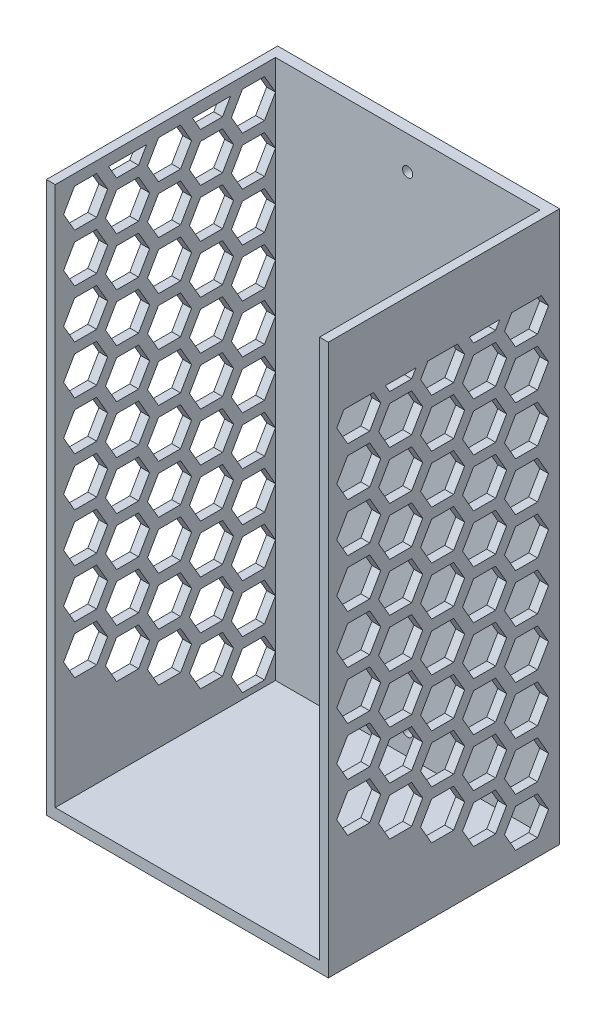
SolidWorks part; units mm, degrees
ref_plane "Front Plane" through (0, 0, 0) normal (0, 0, 1) x (1, 0, 0)
ref_plane "Top Plane" through (0, 0, 0) normal (0, 1, 0) x (1, 0, 0)
ref_plane "Right Plane" through (0, 0, 0) normal (1, 0, 0) x (0, 0, -1)
sketch "Sketch1" plane through (0, 0, 0) normal (0, 0, 1) x (1, 0, 0)
  line L1 (-64, -125) -> (64, -125)
  line L2 (-64, -125) -> (-64, 125)
  line L3 (-64, 125) -> (64, 125)
  line L4 (64, -125) -> (64, 125)
  line L5 (-64, -125) -> (64, 125) construction
  line L6 (-64, 125) -> (64, -125) construction
  point P0 (0, 0)
  dimension "D1" = 128
  dimension "D2" = 250
extrude "Boss-Extrude1" add sketch "Sketch1" along normal blind 5
sketch "Sketch2" plane through (0, 0, 0) normal (0, 0, 1) x (1, 0, 0)
  line L0 (64, 125) -> (-64, 125) construction
  line L1 (-64, -125) -> (64, -125) construction
  circle A0 centre (0, 110) radius 2.3
  circle A1 centre (0, -110) radius 2.3
  dimension "D1" = 4.6
  dimension "D2" = 15
  dimension "D3" = 15
extrude "Cut-Extrude2" cut sketch "Sketch2" along normal through all
sketch "Sketch3" plane through (0, 0, 5) normal (0, 0, 1) x (1, 0, 0)
  line L0 (-64, 125) -> (-64, -125) construction
  line L1 (-64, -121) -> (64, -121)
  line L2 (-64, -121) -> (-64, -125)
  line L3 (-64, -125) -> (64, -125)
  line L4 (64, -121) -> (64, -125)
  dimension "D1" = 4
extrude "Boss-Extrude2" add sketch "Sketch3" along normal blind 100
sketch "Sketch4" plane through (0, 0, 5) normal (0, 0, 1) x (1, 0, 0)
  line L0 (64, -121) -> (-64, -121) construction
  line L1 (-64, 125) -> (-60, 125)
  line L2 (-64, 125) -> (-64, -121)
  line L3 (-64, -121) -> (-60, -121)
  line L4 (-60, 125) -> (-60, -121)
  line L5 (64, -121) -> (-64, -121) construction
  line L6 (64, 125) -> (60, 125)
  line L7 (64, 125) -> (64, -121)
  line L8 (64, -121) -> (60, -121)
  line L9 (60, 125) -> (60, -121)
  dimension "D1" = 4
  dimension "D2" = 4
extrude "Boss-Extrude3" add sketch "Sketch4" along normal up to surface (100 mm away) up to face at (0, -123, 105)
sketch "Sketch5" plane through (-64, 0, 0) normal (-1, 0, 0) x (0, 0, 1)
  line L0 (20, -100) -> (10, -100)
  line L1 (20, 120) -> (10, 120)
  line L2 (10, 120) -> (5, 111.3397)
  line L3 (5, 111.3397) -> (10, 102.6795)
  line L4 (10, 102.6795) -> (20, 102.6795)
  line L5 (20, 102.6795) -> (25, 111.3397)
  line L6 (25, 111.3397) -> (20, 120)
  line L7 (0, 125) -> (0, -125) construction
  line L8 (39.0526, 131) -> (29.0526, 131)
  line L9 (29.0526, 131) -> (24.0526, 122.3397)
  line L10 (24.0526, 122.3397) -> (29.0526, 113.6795)
  line L11 (29.0526, 113.6795) -> (39.0526, 113.6795)
  line L12 (39.0526, 113.6795) -> (44.0526, 122.3397)
  line L13 (44.0526, 122.3397) -> (39.0526, 131)
  line L14 (58.1051, 142) -> (48.1051, 142)
  line L15 (48.1051, 142) -> (43.1051, 133.3397)
  line L16 (43.1051, 133.3397) -> (48.1051, 124.6795)
  line L17 (48.1051, 124.6795) -> (58.1051, 124.6795)
  line L18 (58.1051, 124.6795) -> (63.1051, 133.3397)
  line L19 (63.1051, 133.3397) -> (58.1051, 142)
  line L20 (77.1577, 153) -> (67.1577, 153)
  line L21 (67.1577, 153) -> (62.1577, 144.3397)
  line L22 (62.1577, 144.3397) -> (67.1577, 135.6795)
  line L23 (67.1577, 135.6795) -> (77.1577, 135.6795)
  line L24 (77.1577, 135.6795) -> (82.1577, 144.3397)
  line L25 (82.1577, 144.3397) -> (77.1577, 153)
  line L26 (96.2102, 164) -> (86.2102, 164)
  line L27 (86.2102, 164) -> (81.2102, 155.3397)
  line L28 (81.2102, 155.3397) -> (86.2102, 146.6795)
  line L29 (86.2102, 146.6795) -> (96.2102, 146.6795)
  line L30 (96.2102, 146.6795) -> (101.2102, 155.3397)
  line L31 (101.2102, 155.3397) -> (96.2102, 164)
  line L44 (39.0526, 109) -> (29.0526, 109)
  line L45 (29.0526, 109) -> (24.0526, 100.3397)
  line L46 (24.0526, 100.3397) -> (29.0526, 91.6795)
  line L47 (29.0526, 91.6795) -> (39.0526, 91.6795)
  line L48 (39.0526, 91.6795) -> (44.0526, 100.3397)
  line L49 (44.0526, 100.3397) -> (39.0526, 109)
  line L50 (58.1051, 120) -> (48.1051, 120)
  line L51 (48.1051, 120) -> (43.1051, 111.3397)
  line L52 (43.1051, 111.3397) -> (48.1051, 102.6795)
  line L53 (48.1051, 102.6795) -> (58.1051, 102.6795)
  line L54 (58.1051, 102.6795) -> (63.1051, 111.3397)
  line L55 (63.1051, 111.3397) -> (58.1051, 120)
  line L56 (77.1577, 131) -> (67.1577, 131)
  line L57 (67.1577, 131) -> (62.1577, 122.3397)
  line L58 (62.1577, 122.3397) -> (67.1577, 113.6795)
  line L59 (67.1577, 113.6795) -> (77.1577, 113.6795)
  line L60 (77.1577, 113.6795) -> (82.1577, 122.3397)
  line L61 (82.1577, 122.3397) -> (77.1577, 131)
  line L62 (96.2102, 142) -> (86.2102, 142)
  line L63 (86.2102, 142) -> (81.2102, 133.3397)
  line L64 (81.2102, 133.3397) -> (86.2102, 124.6795)
  line L65 (86.2102, 124.6795) -> (96.2102, 124.6795)
  line L66 (96.2102, 124.6795) -> (101.2102, 133.3397)
  line L67 (101.2102, 133.3397) -> (96.2102, 142)
  line L80 (39.0526, 87) -> (29.0526, 87)
  line L81 (29.0526, 87) -> (24.0526, 78.3397)
  line L82 (24.0526, 78.3397) -> (29.0526, 69.6795)
  line L83 (29.0526, 69.6795) -> (39.0526, 69.6795)
  line L84 (39.0526, 69.6795) -> (44.0526, 78.3397)
  line L85 (44.0526, 78.3397) -> (39.0526, 87)
  line L86 (58.1051, 98) -> (48.1051, 98)
  line L87 (48.1051, 98) -> (43.1051, 89.3397)
  line L88 (43.1051, 89.3397) -> (48.1051, 80.6795)
  line L89 (48.1051, 80.6795) -> (58.1051, 80.6795)
  line L90 (58.1051, 80.6795) -> (63.1051, 89.3397)
  line L91 (63.1051, 89.3397) -> (58.1051, 98)
  line L92 (77.1577, 109) -> (67.1577, 109)
  line L93 (67.1577, 109) -> (62.1577, 100.3397)
  line L94 (62.1577, 100.3397) -> (67.1577, 91.6795)
  line L95 (67.1577, 91.6795) -> (77.1577, 91.6795)
  line L96 (77.1577, 91.6795) -> (82.1577, 100.3397)
  line L97 (82.1577, 100.3397) -> (77.1577, 109)
  line L98 (96.2102, 120) -> (86.2102, 120)
  line L99 (86.2102, 120) -> (81.2102, 111.3397)
  line L100 (81.2102, 111.3397) -> (86.2102, 102.6795)
  line L101 (86.2102, 102.6795) -> (96.2102, 102.6795)
  line L102 (96.2102, 102.6795) -> (101.2102, 111.3397)
  line L103 (101.2102, 111.3397) -> (96.2102, 120)
  line L116 (39.0526, 65) -> (29.0526, 65)
  line L117 (29.0526, 65) -> (24.0526, 56.3397)
  line L118 (24.0526, 56.3397) -> (29.0526, 47.6795)
  line L119 (29.0526, 47.6795) -> (39.0526, 47.6795)
  line L120 (39.0526, 47.6795) -> (44.0526, 56.3397)
  line L121 (44.0526, 56.3397) -> (39.0526, 65)
  line L122 (58.1051, 76) -> (48.1051, 76)
  line L123 (48.1051, 76) -> (43.1051, 67.3397)
  line L124 (43.1051, 67.3397) -> (48.1051, 58.6795)
  line L125 (48.1051, 58.6795) -> (58.1051, 58.6795)
  line L126 (58.1051, 58.6795) -> (63.1051, 67.3397)
  line L127 (63.1051, 67.3397) -> (58.1051, 76)
  line L128 (77.1577, 87) -> (67.1577, 87)
  line L129 (67.1577, 87) -> (62.1577, 78.3397)
  line L130 (62.1577, 78.3397) -> (67.1577, 69.6795)
  line L131 (67.1577, 69.6795) -> (77.1577, 69.6795)
  line L132 (77.1577, 69.6795) -> (82.1577, 78.3397)
  line L133 (82.1577, 78.3397) -> (77.1577, 87)
  line L134 (96.2102, 98) -> (86.2102, 98)
  line L135 (86.2102, 98) -> (81.2102, 89.3397)
  line L136 (81.2102, 89.3397) -> (86.2102, 80.6795)
  line L137 (86.2102, 80.6795) -> (96.2102, 80.6795)
  line L138 (96.2102, 80.6795) -> (101.2102, 89.3397)
  line L139 (101.2102, 89.3397) -> (96.2102, 98)
  line L152 (39.0526, 43) -> (29.0526, 43)
  line L153 (29.0526, 43) -> (24.0526, 34.3397)
  line L154 (24.0526, 34.3397) -> (29.0526, 25.6795)
  line L155 (29.0526, 25.6795) -> (39.0526, 25.6795)
  line L156 (39.0526, 25.6795) -> (44.0526, 34.3397)
  line L157 (44.0526, 34.3397) -> (39.0526, 43)
  line L158 (58.1051, 54) -> (48.1051, 54)
  line L159 (48.1051, 54) -> (43.1051, 45.3397)
  line L160 (43.1051, 45.3397) -> (48.1051, 36.6795)
  line L161 (48.1051, 36.6795) -> (58.1051, 36.6795)
  line L162 (58.1051, 36.6795) -> (63.1051, 45.3397)
  line L163 (63.1051, 45.3397) -> (58.1051, 54)
  line L164 (77.1577, 65) -> (67.1577, 65)
  line L165 (67.1577, 65) -> (62.1577, 56.3397)
  line L166 (62.1577, 56.3397) -> (67.1577, 47.6795)
  line L167 (67.1577, 47.6795) -> (77.1577, 47.6795)
  line L168 (77.1577, 47.6795) -> (82.1577, 56.3397)
  line L169 (82.1577, 56.3397) -> (77.1577, 65)
  line L170 (96.2102, 76) -> (86.2102, 76)
  line L171 (86.2102, 76) -> (81.2102, 67.3397)
  line L172 (81.2102, 67.3397) -> (86.2102, 58.6795)
  line L173 (86.2102, 58.6795) -> (96.2102, 58.6795)
  line L174 (96.2102, 58.6795) -> (101.2102, 67.3397)
  line L175 (101.2102, 67.3397) -> (96.2102, 76)
  line L188 (39.0526, 21) -> (29.0526, 21)
  line L189 (29.0526, 21) -> (24.0526, 12.3397)
  line L190 (24.0526, 12.3397) -> (29.0526, 3.6795)
  line L191 (29.0526, 3.6795) -> (39.0526, 3.6795)
  line L192 (39.0526, 3.6795) -> (44.0526, 12.3397)
  line L193 (44.0526, 12.3397) -> (39.0526, 21)
  line L194 (58.1051, 32) -> (48.1051, 32)
  line L195 (48.1051, 32) -> (43.1051, 23.3397)
  line L196 (43.1051, 23.3397) -> (48.1051, 14.6795)
  line L197 (48.1051, 14.6795) -> (58.1051, 14.6795)
  line L198 (58.1051, 14.6795) -> (63.1051, 23.3397)
  line L199 (63.1051, 23.3397) -> (58.1051, 32)
  line L200 (77.1577, 43) -> (67.1577, 43)
  line L201 (67.1577, 43) -> (62.1577, 34.3397)
  line L202 (62.1577, 34.3397) -> (67.1577, 25.6795)
  line L203 (67.1577, 25.6795) -> (77.1577, 25.6795)
  line L204 (77.1577, 25.6795) -> (82.1577, 34.3397)
  line L205 (82.1577, 34.3397) -> (77.1577, 43)
  line L206 (96.2102, 54) -> (86.2102, 54)
  line L207 (86.2102, 54) -> (81.2102, 45.3397)
  line L208 (81.2102, 45.3397) -> (86.2102, 36.6795)
  line L209 (86.2102, 36.6795) -> (96.2102, 36.6795)
  line L210 (96.2102, 36.6795) -> (101.2102, 45.3397)
  line L211 (101.2102, 45.3397) -> (96.2102, 54)
  line L224 (39.0526, -1) -> (29.0526, -1)
  line L225 (29.0526, -1) -> (24.0526, -9.6603)
  line L226 (24.0526, -9.6603) -> (29.0526, -18.3205)
  line L227 (29.0526, -18.3205) -> (39.0526, -18.3205)
  line L228 (39.0526, -18.3205) -> (44.0526, -9.6603)
  line L229 (44.0526, -9.6603) -> (39.0526, -1)
  line L230 (58.1051, 10) -> (48.1051, 10)
  line L231 (48.1051, 10) -> (43.1051, 1.3397)
  line L232 (43.1051, 1.3397) -> (48.1051, -7.3205)
  line L233 (48.1051, -7.3205) -> (58.1051, -7.3205)
  line L234 (58.1051, -7.3205) -> (63.1051, 1.3397)
  line L235 (63.1051, 1.3397) -> (58.1051, 10)
  line L236 (77.1577, 21) -> (67.1577, 21)
  line L237 (67.1577, 21) -> (62.1577, 12.3397)
  line L238 (62.1577, 12.3397) -> (67.1577, 3.6795)
  line L239 (67.1577, 3.6795) -> (77.1577, 3.6795)
  line L240 (77.1577, 3.6795) -> (82.1577, 12.3397)
  line L241 (82.1577, 12.3397) -> (77.1577, 21)
  line L242 (96.2102, 32) -> (86.2102, 32)
  line L243 (86.2102, 32) -> (81.2102, 23.3397)
  line L244 (81.2102, 23.3397) -> (86.2102, 14.6795)
  line L245 (86.2102, 14.6795) -> (96.2102, 14.6795)
  line L246 (96.2102, 14.6795) -> (101.2102, 23.3397)
  line L247 (101.2102, 23.3397) -> (96.2102, 32)
  line L260 (39.0526, -23) -> (29.0526, -23)
  line L261 (29.0526, -23) -> (24.0526, -31.6603)
  line L262 (24.0526, -31.6603) -> (29.0526, -40.3205)
  line L263 (29.0526, -40.3205) -> (39.0526, -40.3205)
  line L264 (39.0526, -40.3205) -> (44.0526, -31.6603)
  line L265 (44.0526, -31.6603) -> (39.0526, -23)
  line L266 (58.1051, -12) -> (48.1051, -12)
  line L267 (48.1051, -12) -> (43.1051, -20.6603)
  line L268 (43.1051, -20.6603) -> (48.1051, -29.3205)
  line L269 (48.1051, -29.3205) -> (58.1051, -29.3205)
  line L270 (58.1051, -29.3205) -> (63.1051, -20.6603)
  line L271 (63.1051, -20.6603) -> (58.1051, -12)
  line L272 (77.1577, -1) -> (67.1577, -1)
  line L273 (67.1577, -1) -> (62.1577, -9.6603)
  line L274 (62.1577, -9.6603) -> (67.1577, -18.3205)
  line L275 (67.1577, -18.3205) -> (77.1577, -18.3205)
  line L276 (77.1577, -18.3205) -> (82.1577, -9.6603)
  line L277 (82.1577, -9.6603) -> (77.1577, -1)
  line L278 (96.2102, 10) -> (86.2102, 10)
  line L279 (86.2102, 10) -> (81.2102, 1.3397)
  line L280 (81.2102, 1.3397) -> (86.2102, -7.3205)
  line L281 (86.2102, -7.3205) -> (96.2102, -7.3205)
  line L282 (96.2102, -7.3205) -> (101.2102, 1.3397)
  line L283 (101.2102, 1.3397) -> (96.2102, 10)
  line L296 (39.0526, -45) -> (29.0526, -45)
  line L297 (29.0526, -45) -> (24.0526, -53.6603)
  line L298 (24.0526, -53.6603) -> (29.0526, -62.3205)
  line L299 (29.0526, -62.3205) -> (39.0526, -62.3205)
  line L300 (39.0526, -62.3205) -> (44.0526, -53.6603)
  line L301 (44.0526, -53.6603) -> (39.0526, -45)
  line L302 (58.1051, -34) -> (48.1051, -34)
  line L303 (48.1051, -34) -> (43.1051, -42.6603)
  line L304 (43.1051, -42.6603) -> (48.1051, -51.3205)
  line L305 (48.1051, -51.3205) -> (58.1051, -51.3205)
  line L306 (58.1051, -51.3205) -> (63.1051, -42.6603)
  line L307 (63.1051, -42.6603) -> (58.1051, -34)
  line L308 (77.1577, -23) -> (67.1577, -23)
  line L309 (67.1577, -23) -> (62.1577, -31.6603)
  line L310 (62.1577, -31.6603) -> (67.1577, -40.3205)
  line L311 (67.1577, -40.3205) -> (77.1577, -40.3205)
  line L312 (77.1577, -40.3205) -> (82.1577, -31.6603)
  line L313 (82.1577, -31.6603) -> (77.1577, -23)
  line L314 (96.2102, -12) -> (86.2102, -12)
  line L315 (86.2102, -12) -> (81.2102, -20.6603)
  line L316 (81.2102, -20.6603) -> (86.2102, -29.3205)
  line L317 (86.2102, -29.3205) -> (96.2102, -29.3205)
  line L318 (96.2102, -29.3205) -> (101.2102, -20.6603)
  line L319 (101.2102, -20.6603) -> (96.2102, -12)
  line L332 (39.0526, -67) -> (29.0526, -67)
  line L333 (29.0526, -67) -> (24.0526, -75.6603)
  line L334 (24.0526, -75.6603) -> (29.0526, -84.3205)
  line L335 (29.0526, -84.3205) -> (39.0526, -84.3205)
  line L336 (39.0526, -84.3205) -> (44.0526, -75.6603)
  line L337 (44.0526, -75.6603) -> (39.0526, -67)
  line L338 (58.1051, -56) -> (48.1051, -56)
  line L339 (48.1051, -56) -> (43.1051, -64.6603)
  line L340 (43.1051, -64.6603) -> (48.1051, -73.3205)
  line L341 (48.1051, -73.3205) -> (58.1051, -73.3205)
  line L342 (58.1051, -73.3205) -> (63.1051, -64.6603)
  line L343 (63.1051, -64.6603) -> (58.1051, -56)
  line L344 (77.1577, -45) -> (67.1577, -45)
  line L345 (67.1577, -45) -> (62.1577, -53.6603)
  line L346 (62.1577, -53.6603) -> (67.1577, -62.3205)
  line L347 (67.1577, -62.3205) -> (77.1577, -62.3205)
  line L348 (77.1577, -62.3205) -> (82.1577, -53.6603)
  line L349 (82.1577, -53.6603) -> (77.1577, -45)
  line L350 (96.2102, -34) -> (86.2102, -34)
  line L351 (86.2102, -34) -> (81.2102, -42.6603)
  line L352 (81.2102, -42.6603) -> (86.2102, -51.3205)
  line L353 (86.2102, -51.3205) -> (96.2102, -51.3205)
  line L354 (96.2102, -51.3205) -> (101.2102, -42.6603)
  line L355 (101.2102, -42.6603) -> (96.2102, -34)
  line L512 (20, 98) -> (10, 98)
  line L513 (10, 98) -> (5, 89.3397)
  line L514 (5, 89.3397) -> (10, 80.6795)
  line L515 (10, 80.6795) -> (20, 80.6795)
  line L516 (20, 80.6795) -> (25, 89.3397)
  line L517 (25, 89.3397) -> (20, 98)
  line L518 (20, 76) -> (10, 76)
  line L519 (10, 76) -> (5, 67.3397)
  line L520 (5, 67.3397) -> (10, 58.6795)
  line L521 (10, 58.6795) -> (20, 58.6795)
  line L522 (20, 58.6795) -> (25, 67.3397)
  line L523 (25, 67.3397) -> (20, 76)
  line L524 (20, 54) -> (10, 54)
  line L525 (10, 54) -> (5, 45.3397)
  line L526 (5, 45.3397) -> (10, 36.6795)
  line L527 (10, 36.6795) -> (20, 36.6795)
  line L528 (20, 36.6795) -> (25, 45.3397)
  line L529 (25, 45.3397) -> (20, 54)
  line L530 (20, 32) -> (10, 32)
  line L531 (10, 32) -> (5, 23.3397)
  line L532 (5, 23.3397) -> (10, 14.6795)
  line L533 (10, 14.6795) -> (20, 14.6795)
  line L534 (20, 14.6795) -> (25, 23.3397)
  line L535 (25, 23.3397) -> (20, 32)
  line L536 (20, 10) -> (10, 10)
  line L537 (10, 10) -> (5, 1.3397)
  line L538 (5, 1.3397) -> (10, -7.3205)
  line L539 (10, -7.3205) -> (20, -7.3205)
  line L540 (20, -7.3205) -> (25, 1.3397)
  line L541 (25, 1.3397) -> (20, 10)
  line L542 (20, -12) -> (10, -12)
  line L543 (10, -12) -> (5, -20.6603)
  line L544 (5, -20.6603) -> (10, -29.3205)
  line L545 (10, -29.3205) -> (20, -29.3205)
  line L546 (20, -29.3205) -> (25, -20.6603)
  line L547 (25, -20.6603) -> (20, -12)
  line L548 (20, -34) -> (10, -34)
  line L549 (10, -34) -> (5, -42.6603)
  line L550 (5, -42.6603) -> (10, -51.3205)
  line L551 (10, -51.3205) -> (20, -51.3205)
  line L552 (20, -51.3205) -> (25, -42.6603)
  line L553 (25, -42.6603) -> (20, -34)
  line L554 (20, -56) -> (10, -56)
  line L555 (10, -56) -> (5, -64.6603)
  line L556 (5, -64.6603) -> (10, -73.3205)
  line L557 (10, -73.3205) -> (20, -73.3205)
  line L558 (20, -73.3205) -> (25, -64.6603)
  line L559 (25, -64.6603) -> (20, -56)
  line L560 (20, -78) -> (10, -78)
  line L561 (10, -78) -> (5, -86.6603)
  line L562 (5, -86.6603) -> (10, -95.3205)
  line L563 (10, -95.3205) -> (20, -95.3205)
  line L564 (20, -95.3205) -> (25, -86.6603)
  line L565 (25, -86.6603) -> (20, -78)
  line L590 (20, 120) -> (39.0526, 131) construction
  line L591 (105, 125) -> (0, 125) construction
  line L592 (10, -100) -> (5, -108.6603)
  line L593 (5, -108.6603) -> (10, -117.3205)
  line L594 (10, -117.3205) -> (20, -117.3205)
  line L595 (20, -117.3205) -> (25, -108.6603)
  line L596 (25, -108.6603) -> (20, -100)
  line L597 (39.0526, -89) -> (29.0526, -89)
  line L598 (29.0526, -89) -> (24.0526, -97.6603)
  line L599 (24.0526, -97.6603) -> (29.0526, -106.3205)
  line L600 (29.0526, -106.3205) -> (39.0526, -106.3205)
  line L601 (39.0526, -106.3205) -> (44.0526, -97.6603)
  line L602 (44.0526, -97.6603) -> (39.0526, -89)
  line L603 (58.1051, -78) -> (48.1051, -78)
  line L604 (48.1051, -78) -> (43.1051, -86.6603)
  line L605 (43.1051, -86.6603) -> (48.1051, -95.3205)
  line L606 (48.1051, -95.3205) -> (58.1051, -95.3205)
  line L607 (58.1051, -95.3205) -> (63.1051, -86.6603)
  line L608 (63.1051, -86.6603) -> (58.1051, -78)
  line L609 (77.1577, -67) -> (67.1577, -67)
  line L610 (67.1577, -67) -> (62.1577, -75.6603)
  line L611 (62.1577, -75.6603) -> (67.1577, -84.3205)
  line L612 (67.1577, -84.3205) -> (77.1577, -84.3205)
  line L613 (77.1577, -84.3205) -> (82.1577, -75.6603)
  line L614 (82.1577, -75.6603) -> (77.1577, -67)
  line L615 (96.2102, -56) -> (86.2102, -56)
  line L616 (86.2102, -56) -> (81.2102, -64.6603)
  line L617 (81.2102, -64.6603) -> (86.2102, -73.3205)
  line L618 (86.2102, -73.3205) -> (96.2102, -73.3205)
  line L619 (96.2102, -73.3205) -> (101.2102, -64.6603)
  line L620 (101.2102, -64.6603) -> (96.2102, -56)
  circle A0 centre (15, 111.3397) radius 8.6603 construction
  dimension "D1" = 10
  dimension "D2" = 5
  dimension "D3" = 15
  dimension "D6" = 22
  dimension "D4" = 5
  dimension "D5" = 11
extrude "Cut-Extrude3" cut sketch "Sketch5" against normal through all
sketch "Sketch6" plane through (-64, 0, 0) normal (-1, 0, 0) x (0, 0, 1)
  line L0 (105, 125) -> (105, -125)
  line L1 (0, 125) -> (105, 125)
  line L2 (0, 125) -> (0, 120)
  line L3 (0, 120) -> (102, 120)
  line L5 (0, -125) -> (105, -125)
  line L6 (0, -125) -> (0, -120)
  line L7 (0, -120) -> (102, -120)
  line L12 (102, 120) -> (102, -120)
  line L13 (105, 125) -> (105, -125) construction
  dimension "D1" = 5
  dimension "D2" = 3
  dimension "D3" = 5
extrude "Boss-Extrude4" add sketch "Sketch6" against normal up to surface (4 mm away) up to face at (-60, 89.3397, 91.2102)
sketch "Sketch7" plane through (64, 0, 0) normal (1, 0, 0) x (0, 0, -1)
  line L1 (0, -125) -> (-105, -125)
  line L2 (0, -125) -> (0, -120)
  line L3 (0, -120) -> (-105, -120)
  line L4 (-105, -125) -> (-105, -120)
  dimension "D1" = 5
extrude "Boss-Extrude5" add sketch "Sketch7" against normal up to surface (128 mm away) up to face at (-64, 111.3397, 91.2102)
sketch "Sketch8" plane through (64, 0, 0) normal (1, 0, 0) x (0, 0, -1)
  line L5 (-105, 125) -> (-105, -125)
  line L10 (0, 125) -> (-105, 125)
  line L11 (0, 125) -> (0, 95)
  line L12 (0, 95) -> (-102, 95)
  line L14 (-105, -125) -> (-105, 125) construction
  line L15 (-105, -125) -> (-102, -125)
  line L16 (-102, -125) -> (-102, 95)
  line L17 (-105, -125) -> (0, -125) construction
  dimension "D1" = 3
extrude "Boss-Extrude6" add sketch "Sketch8" against normal up to surface (4 mm away) up to face at (60, 89.3397, 91.2102)
